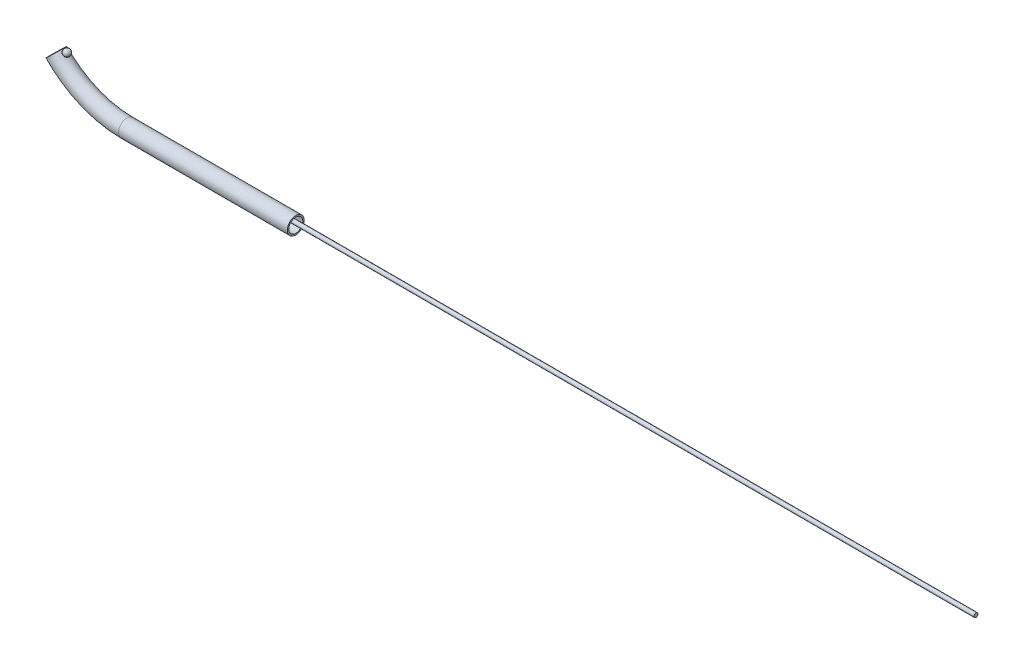
SolidWorks part; units mm, degrees
ref_plane "Front Plane" through (0, 0, 0) normal (0, 0, 1) x (1, 0, 0)
ref_plane "Top Plane" through (0, 0, 0) normal (0, 1, 0) x (1, 0, 0)
ref_plane "Right Plane" through (0, 0, 0) normal (1, 0, 0) x (0, 0, -1)
ref_axis "Axis1" through (-88.99, 0, 0) along (1, 0, 0)
sketch "Sketch4" plane through (0, 0, 0) normal (0, 0, 1) x (1, 0, 0)
  line L0 (-218.053, 283.5718) -> (61.923, 683.419) construction
  line L1 (-68.365, 0) -> (-65.9542, 0)
  arc A0 (-68.365, 0) -> (-73.5499, 2.2253) centre (-68.365, 7.1532) cw
  point P2 (-73.5499, 2.2253)
  point P3 (-68.365, 0)
sketch "Sketch1" plane through (0, 0, 0) normal (1, 0, 0) x (0, 0, -1)
  circle A0 centre (0, 0) radius 0.61
  circle A1 centre (0, 0) radius 0.39
  dimension "D1" = 1.22
  dimension "D2" = 0.22
extrude "Boss-Extrude1" [suppressed] add sketch "Sketch1" along normal blind 10
ref_plane "Plane1" through (-65.9542, 0, 0) normal (1, 0, 0) x (0, 0, -1)
sketch "Sketch5" plane through (-65.9542, 0, 0) normal (1, 0, 0) x (0, 0, -1)
  circle A0 centre (0, 0) radius 0.6223
  circle A1 centre (0, 0) radius 0.5143
  dimension "D1" = 1.2446
  dimension "D2" = 1.0287
sweep "Sweep2" add profiles "Sketch5" path "Sketch4"
extrude "Boss-Extrude2" add sketch "Sketch5<2>" along normal blind 10
sketch "Sketch5<2>" plane through (-65.9542, 0, 0) normal (1, 0, 0) x (0, 0, -1) same geometry as "Sketch5"
sketch "Sketch6" plane through (0, 0, 0) normal (0, 0, 1) x (1, 0, 0)
  line L0 (-72.7874, 2.8286) -> (-72.7874, 2.3286) construction
  line L1 (-72.9491, 2.3879) -> (-72.6257, 2.7693)
  circle A0 centre (-72.7874, 2.5786) radius 0.25 construction
  arc A1 (-72.9491, 2.3879) -> (-72.6257, 2.7693) centre (-72.7874, 2.5786) ccw
  dimension "D1" = 0.5
revolve "Revolve2" add sketch "Sketch6" angle 360 about L1
sketch "Sketch7" plane through (0, 0, 0) normal (0, 0, 1) x (1, 0, 0)
  line L0 (-68.365, -0.6223) -> (-55.9542, -0.6223) construction
  line L1 (-68.365, -0.6223) -> (-55.9542, -0.6223) construction
  line L2 (-68.365, 0.1777) -> (-55.9542, 0.1777)
  arc A1 (-74.001, 1.7966) -> (-68.365, -0.6223) centre (-68.365, 7.1532) ccw construction
  arc A2 (-74.001, 1.7966) -> (-68.365, -0.6223) centre (-68.365, 7.1532) ccw construction
  arc A3 (-73.4211, 2.3477) -> (-68.365, 0.1777) centre (-68.365, 7.1532) ccw
  dimension "D1" = 0.8
sketch "Sketch8" plane through (-36.0182, 37.8966, 0) normal (-0.6889, 0.7248, 0) x (0.7248, 0.6889, 0)
  circle A0 centre (-51.6014, 0) radius 0.15
  point P0 (-51.6014, 0)
  dimension "D1" = 0.3
sweep "Sweep3" add profiles "Sketch8" path "Sketch7"
sketch "Sketch9" plane through (-55.9542, 0, 0) normal (1, 0, 0) x (0, 0, -1)
  circle A0 centre (0, 0.1777) radius 0.15 construction
  circle A1 centre (0, 0.1777) radius 0.15
extrude "Boss-Extrude3" add sketch "Sketch9" along normal blind 50
